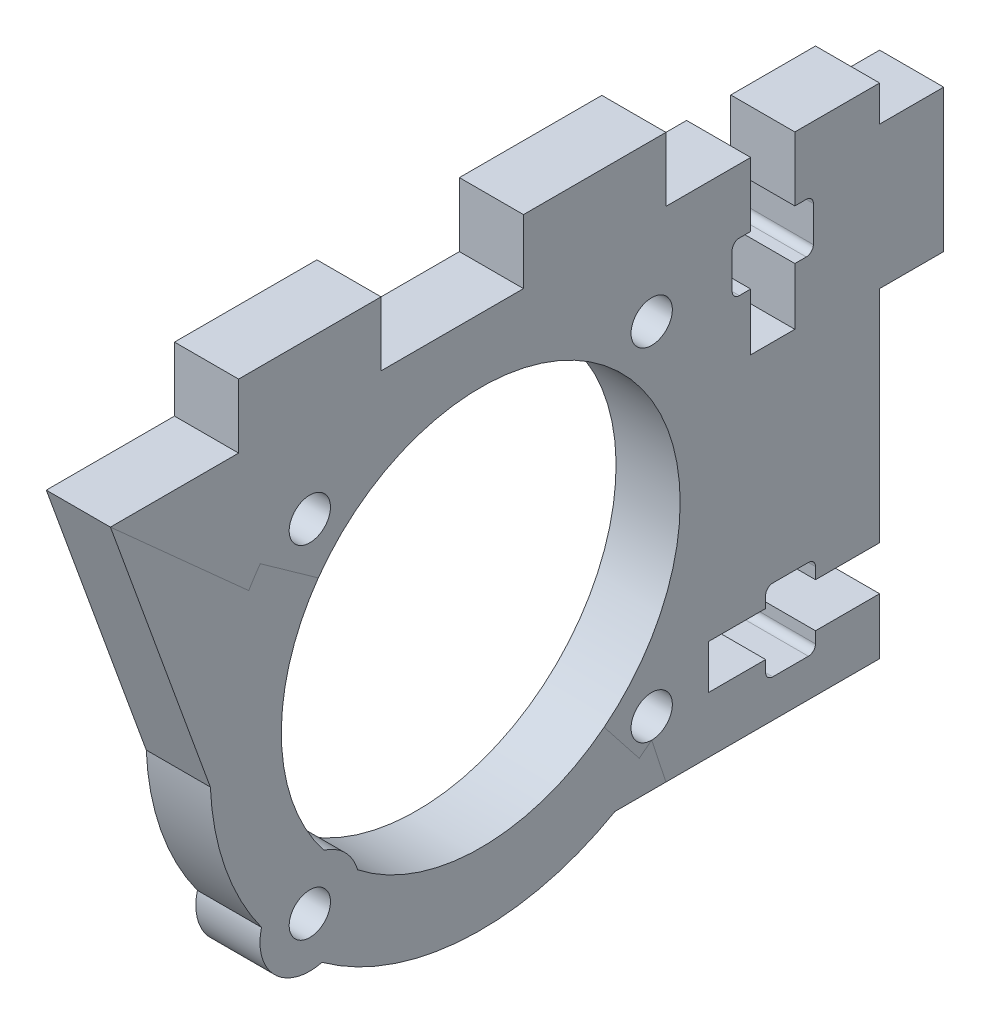
SolidWorks part; units mm, degrees
ref_plane "Front Plane" through (0, 0, 0) normal (0, 0, 1) x (1, 0, 0)
ref_plane "Top Plane" through (0, 0, 0) normal (0, 1, 0) x (1, 0, 0)
ref_plane "Right Plane" through (0, 0, 0) normal (1, 0, 0) x (0, 0, -1)
sketch "Sketch1" plane through (0, 0, 0) normal (1, 0, 0) x (0, 0, -1)
  line L0 (0, 0) -> (0, -35)
  line L1 (0, -35) -> (-54, 0)
  line L2 (-54, 0) -> (0, 0)
  dimension "D1" = 35
  dimension "D2" = 54
extrude "Boss-Extrude1" add sketch "Sketch1" along normal blind 4.5
sketch "Sketch2" plane through (4.5, 0, 0) normal (1, 0, 0) x (0, 0, -1)
  line L0 (0, -35) -> (0, 0) construction
  line L1 (-4.5, -2.5) -> (4.5, -2.5)
  line L2 (-4.5, -2.5) -> (-4.5, -12.5)
  line L3 (-4.5, -12.5) -> (4.5, -12.5)
  line L4 (4.5, -2.5) -> (4.5, -12.5)
  line L5 (-4.5, -2.5) -> (4.5, -12.5) construction
  line L6 (-4.5, -12.5) -> (4.5, -2.5) construction
  line L7 (0, 0) -> (-54, 0) construction
  point P0 (0, -7.5)
  dimension "D1" = 10
  dimension "D2" = 7.5
  dimension "D3" = 4.5
extrude "Boss-Extrude2" add sketch "Sketch2" against normal through all
sketch "Sketch3" plane through (4.5, 0, 0) normal (1, 0, 0) x (0, 0, -1)
  line L0 (0, -35) -> (-15, -35)
  line L1 (0, -25) -> (-54, 0)
  line L4 (0, -35) -> (0, -12.5) construction
  line L5 (0, -25) -> (0, -35)
  line L6 (-54, 0) -> (-15, -35)
  dimension "D1" = 15
  dimension "D2" = 10
extrude "Boss-Extrude3" add sketch "Sketch3" against normal through all
sketch "Sketch4" plane through (4.5, 0, 0) normal (1, 0, 0) x (0, 0, -1)
  line L0 (0, -29.5) -> (-12, -29.5) construction
  line L1 (0, -35) -> (0, -12.5) construction
  line L2 (0, -27.95) -> (-12, -27.95) construction
  line L3 (-12, -27.95) -> (-12, -31.05) construction
  line L4 (0, -31.05) -> (0, -27.95)
  line L5 (0, -27.95) -> (-4.5, -27.95)
  line L6 (-4.5, -27.95) -> (-4.5, -27.15)
  line L7 (-5, -26.65) -> (-7.5, -26.65)
  line L8 (-8, -27.15) -> (-8, -27.95)
  line L9 (-8, -27.95) -> (-12, -27.95)
  line L10 (-12, -27.95) -> (-12, -31.05)
  line L12 (0, -31.05) -> (-12, -31.05) construction
  line L13 (-8, -31.05) -> (-12, -31.05)
  line L14 (-8, -31.85) -> (-8, -31.05)
  line L15 (-5, -32.35) -> (-7.5, -32.35)
  line L16 (-4.5, -31.05) -> (-4.5, -31.85)
  line L17 (0, -31.05) -> (-4.5, -31.05)
  line L18 (4.5, -12.5) -> (4.5, -2.5) construction
  line L19 (0, -18.5) -> (-33.3857, -18.5) construction
  line L20 (-54, 0) -> (-15, -35) construction
  line L37 (0, -31.05) -> (-12, -31.05) construction
  arc A0 (-8, -31.85) -> (-7.5, -32.35) centre (-7.5, -31.85) ccw
  arc A1 (-5, -32.35) -> (-4.5, -31.85) centre (-5, -31.85) ccw
  arc A2 (-4.5, -27.15) -> (-5, -26.65) centre (-5, -27.15) ccw
  arc A3 (-7.5, -26.65) -> (-8, -27.15) centre (-7.5, -27.15) ccw
  point P10 (4.5, -7.5)
  point P20 (-8, -32.35)
  point P23 (-4.5, -32.35)
  point P26 (-4.5, -26.65)
  point P29 (-8, -26.65)
  dimension "D7" = 0.5
  dimension "D1" = 12
  dimension "D2" = 1.55
  dimension "D3" = 2.85
  dimension "D4" = 3.5
  dimension "D5" = 8
  dimension "D6" = 22
extrude "Cut-Extrude1" cut sketch "Sketch4" against normal through all
sketch "Sketch5" plane through (4.5, 0, 0) normal (1, 0, 0) x (0, 0, -1)
  line L0 (0, 0) -> (-54, 0) construction
  line L1 (-25, 4.5) -> (-15, 4.5)
  line L2 (-25, 4.5) -> (-25, 0)
  line L3 (0, 0) -> (-54, 0) construction
  line L4 (-15, 4.5) -> (-15, 0)
  line L5 (-25, 4.5) -> (-20, 0) construction
  line L6 (-20, 0) -> (-15, 4.5) construction
  line L7 (-30, 0) -> (-30, 4.5) construction
  line L8 (-40, 0) -> (-45, 4.5) construction
  line L9 (-35, 4.5) -> (-40, 0) construction
  line L10 (-45, 4.5) -> (-45, 0)
  line L12 (-35, 4.5) -> (-35, 0)
  line L13 (-35, 4.5) -> (-45, 4.5)
  line L14 (-20, 0) -> (-15, 4.5) construction
  line L15 (-15, 0) -> (-25, 0)
  line L16 (-35, 0) -> (-45, 0)
  point P0 (-20, 0)
  point P14 (-40, 0)
  dimension "D3" = 4.5
  dimension "D1" = 20
  dimension "D2" = 10
  dimension "D4" = 20
  dimension "D5" = 5
extrude "Boss-Extrude4" add sketch "Sketch5" against normal through all
sketch "Sketch8" [suppressed] plane through (4.5, 0, 0) normal (1, 0, 0) x (0, 0, -1)
  line L0 (-15, -30) -> (-27, -30) construction
  line L1 (-15, -35) -> (-27, -35)
  line L2 (-15, -25) -> (-27, -25)
  line L3 (-15, -35) -> (0, -35) construction
  line L4 (-15, -25) -> (-15, -35)
  arc A1 (-27, -25) -> (-27, -35) centre (-27, -30) ccw
  dimension "D5" = 5
  dimension "D1" = 0
  dimension "D2" = 12
  dimension "D3" = 0
  dimension "D4" = 10
extrude "Boss-Extrude5" [suppressed] add sketch "Sketch8" against normal up to surface (4.5 mm away) up to face at (0, -17.3125, 11.9375)
sketch "Sketch9" [suppressed] plane through (4.5, 0, 0) normal (1, 0, 0) x (0, 0, -1)
  line L0 (-27, -30) -> (-22, -30) construction
  line L1 (-27, -27) -> (-22, -27)
  line L2 (-27, -33) -> (-22, -33)
  arc A0 (-27, -27) -> (-27, -33) centre (-27, -30) ccw
  arc A1 (-22, -33) -> (-22, -27) centre (-22, -30) ccw
  point P3 (-24.5, -30)
  dimension "D1" = 3
  dimension "D2" = 5
extrude "Cut-Extrude3" [suppressed] cut sketch "Sketch9" against normal through all
sketch "Sketch10" plane through (0, 0, 0) normal (-1, 0, 0) x (0, 0, 1)
  line L0 (15, -35) -> (54, -12)
  line L1 (54, -12) -> (54, 0)
  line L3 (54, 0) -> (15, -35)
  dimension "D1" = 12
extrude "Boss-Extrude6" [suppressed] add sketch "Sketch10" against normal through all
sketch "Sketch6" plane through (4.5, 0, 0) normal (1, 0, 0) x (0, 0, -1)
  line L0 (-30, 0) -> (-30, -11) construction
  line L1 (-25, 0) -> (-35, 0) construction
  line L2 (-28.45, -11) -> (-31.55, -11) construction
  line L3 (-31.55, -11) -> (-31.55, 0) construction
  line L4 (-28.45, 0) -> (-31.55, 0)
  line L5 (-31.55, 0) -> (-31.55, -4.5)
  line L6 (-31.55, -4.5) -> (-32.35, -4.5)
  line L7 (-32.85, -5) -> (-32.85, -7.5)
  line L8 (-32.35, -8) -> (-31.55, -8)
  line L9 (-31.55, -8) -> (-31.55, -11)
  line L10 (-31.55, -11) -> (-28.45, -11)
  line L11 (-28.45, -11) -> (-28.45, 0) construction
  line L12 (-28.45, -8) -> (-28.45, -11)
  line L13 (-27.65, -8) -> (-28.45, -8)
  line L14 (-27.15, -5) -> (-27.15, -7.5)
  line L15 (-28.45, -4.5) -> (-27.65, -4.5)
  line L16 (-28.45, 0) -> (-28.45, -4.5)
  arc A0 (-32.85, -7.5) -> (-32.35, -8) centre (-32.35, -7.5) ccw
  arc A1 (-32.35, -4.5) -> (-32.85, -5) centre (-32.35, -5) ccw
  arc A2 (-27.65, -4.5) -> (-27.15, -5) centre (-27.65, -5) cw
  arc A3 (-27.15, -7.5) -> (-27.65, -8) centre (-27.65, -7.5) cw
  point P12 (-32.85, -8)
  point P15 (-32.85, -4.5)
  point P26 (-27.15, -4.5)
  point P27 (-27.15, -8)
  dimension "D2" = 1.55
  dimension "D4" = 3.5
  dimension "D6" = 0.5
  dimension "D1" = 11
  dimension "D3" = 8
  dimension "D5" = 2.85
extrude "Cut-Extrude2" [suppressed] cut sketch "Sketch6" against normal through all
sketch "Sketch11" plane through (0, 0, 0) normal (-1, 0, 0) x (0, 0, 1)
  line L0 (7.5, 0) -> (7.5, -12) construction
  line L1 (0, 0) -> (15, 0) construction
  line L2 (5.95, -12) -> (9.05, -12)
  line L3 (9.05, -12) -> (9.05, -8)
  line L4 (9.05, -8) -> (9.85, -8)
  line L5 (10.35, -7.5) -> (10.35, -5)
  line L6 (9.85, -4.5) -> (9.05, -4.5)
  line L7 (9.05, -4.5) -> (9.05, 0)
  line L8 (9.05, 0) -> (5.95, 0)
  line L9 (9.05, -8) -> (9.05, -4.5) construction
  line L10 (0, 0) -> (15, 0) construction
  line L11 (5.95, -8) -> (5.95, -4.5) construction
  line L12 (5.95, -4.5) -> (5.95, 0)
  line L13 (5.15, -4.5) -> (5.95, -4.5)
  line L14 (4.65, -7.5) -> (4.65, -5)
  line L15 (5.95, -8) -> (5.15, -8)
  line L16 (5.95, -12) -> (5.95, -8)
  arc A0 (10.35, -5) -> (9.85, -4.5) centre (9.85, -5) ccw
  arc A1 (5.15, -4.5) -> (4.65, -5) centre (5.15, -5) ccw
  arc A2 (9.85, -8) -> (10.35, -7.5) centre (9.85, -7.5) ccw
  arc A3 (4.65, -7.5) -> (5.15, -8) centre (5.15, -7.5) ccw
  point P11 (7.5, 0)
  point P22 (10.35, -4.5)
  point P25 (4.65, -4.5)
  point P28 (10.35, -8)
  point P31 (4.65, -8)
  dimension "D7" = 0.5
  dimension "D1" = 12
  dimension "D3" = 2.85
  dimension "D8" = 0.5
  dimension "D2" = 3.5
  dimension "D4" = 8
  dimension "D5" = 1.55
  dimension "D6" = 0
extrude "Cut-Extrude4" cut sketch "Sketch11" against normal through all
sketch "Sketch12" plane through (0, 0, 0) normal (-1, 0, 0) x (0, 0, 1)
  line L0 (28, -18.5) -> (16, -6.5) construction
  line L1 (28, -18.5) -> (28, -4.5) construction
  line L2 (28, -18.5) -> (40, -6.5) construction
  line L3 (28, -18.5) -> (14, -18.5) construction
  line L4 (28, -18.5) -> (16, -30.5) construction
  line L5 (28, -18.5) -> (16, -6.5) construction
  line L6 (0, -27.95) -> (0, -12.5) construction
  line L7 (25, 0) -> (35, 0) construction
  circle A0 centre (28, -18.5) radius 14
  circle A1 centre (16, -6.5) radius 1.45
  circle A2 centre (40, -6.5) radius 1.45
  circle A3 centre (16, -30.5) radius 1.45
  dimension "D1" = 28
  dimension "D2" = 2.9
  dimension "D3" = 12
  dimension "D4" = 45
  dimension "D5" = 28
  dimension "D6" = 18.5
extrude "FanCutout" cut sketch "Sketch12" against normal through all
sketch "Sketch13" plane through (0, 0, 0) normal (-1, 0, 0) x (0, 0, 1)
  line L0 (39.4071, -10.3834) -> (43.481, -7.4847)
  line L1 (19.3358, -29.4969) -> (16.2414, -33.4243)
  line L6 (28, -18.5) -> (54, 0) construction
  line L7 (28, -18.5) -> (15, -35) construction
  arc A0 (19.3358, -29.4969) -> (39.4071, -10.3834) centre (28, -18.5) ccw
  arc A1 (16.2414, -33.4243) -> (43.481, -7.4847) centre (28, -18.5) ccw
  arc A3 (40.4722, -12.1404) -> (20.333, -30.214) centre (28, -18.5) ccw construction
  dimension "D1" = 5
extrude "Boss-Extrude7" add sketch "Sketch13" against normal through all
sketch "Sketch14" plane through (0, 0, 0) normal (-1, 0, 0) x (0, 0, 1)
  line L0 (28, -4.5) -> (28, -32.5) construction
  line L1 (28, -18.5) -> (40, -30.5) construction
  circle A0 centre (28, -18.5) radius 14 construction
  circle A1 centre (40, -30.5) radius 3.5
  dimension "D2" = 7
  dimension "D1" = 45
  dimension "D3" = 12
extrude "Boss-Extrude8" add sketch "Sketch14" against normal through all
sketch "Sketch15" plane through (0, 0, 0) normal (-1, 0, 0) x (0, 0, 1)
  line L0 (42.4749, -32.9749) -> (28, -18.5) construction
  arc A0 (39.1388, -33.8924) -> (43.3924, -29.6388) centre (40, -30.5) ccw construction
  circle A1 centre (40, -30.5) radius 1.45
  dimension "D1" = 2.9
extrude "Cut-Extrude6" cut sketch "Sketch15" against normal through all
sketch "Sketch16" [suppressed] plane through (4.5, 0, 0) normal (1, 0, 0) x (0, 0, -1)
  line L0 (0, -34.5) -> (-39, -34.5) construction
  line L1 (0, -27.95) -> (0, -12.5) construction
  line L2 (-15, -34.5) -> (-39, -34.5) construction
  line L3 (-15, -38.5) -> (-39, -38.5)
  line L4 (-15, -30.5) -> (-39, -30.5)
  arc A0 (-15, -38.5) -> (-15, -30.5) centre (-15, -34.5) ccw
  arc A1 (-39, -30.5) -> (-39, -38.5) centre (-39, -34.5) ccw
  point P5 (-27, -34.5)
  point P12 (0, -20.225)
  dimension "D1" = 4
  dimension "D2" = 34.5
  dimension "D3" = 39
  dimension "D4" = 15
extrude "Boss-Extrude9" [suppressed] add sketch "Sketch16" against normal through all
sketch "Sketch17" [suppressed] plane through (4.5, 0, 0) normal (1, 0, 0) x (0, 0, -1)
  line L0 (-43, -34.5) -> (0, -34.5) construction
  line L1 (0, -27.75) -> (0, -12.5) construction
  line L2 (-26.5, -34.5) -> (-26.5, -20.0064) construction
  arc A0 (-42.1823, -32.0766) -> (-39, -38.5) centre (-39, -34.5) ccw construction
  circle A1 centre (-39, -34.5) radius 1.55
  circle A2 centre (-14, -34.5) radius 1.55
  dimension "D1" = 2.9
  dimension "D2" = 12.5
extrude "Cut-Extrude7" [suppressed] cut sketch "Sketch17" against normal through all
sketch "Sketch18" [suppressed] plane through (4.5, 0, 0) normal (1, 0, 0) x (0, 0, -1)
  line L0 (-15, -38.5) -> (0, -35)
  line L1 (0, -35) -> (-11.0314, -35)
  line L2 (-11.0314, -35) -> (-15, -38.5)
extrude "Boss-Extrude10" [suppressed] add sketch "Sketch18" against normal through all
sketch "Sketch20" [suppressed] plane through (4.5, 0, 0) normal (1, 0, 0) x (0, 0, -1)
  line L0 (0, -35) -> (0, -31.05) construction
  line L1 (-9, -38) -> (-37.9081, -38)
  line L2 (-40.7232, -36.0371) -> (-54, 0)
  line L3 (-54, 0) -> (-15, -35)
  line L4 (-15, -35) -> (-6, -35)
  line L5 (-9, -38) -> (-6, -35)
  line L6 (-40.7232, -36.0371) -> (-40, -38) construction
  line L7 (-40, -38) -> (-37.9081, -38) construction
  arc A1 (-37.9081, -38) -> (-40.7232, -36.0371) centre (-37.9081, -35) cw
  point P0 (0, -33.025)
  point P14 (-40, -38)
  dimension "D3" = 6
  dimension "D4" = 3
  dimension "D1" = 40
  dimension "D2" = 3
  dimension "D5" = 135
extrude "Boss-Extrude11" [suppressed] add sketch "Sketch20" against normal through all
sketch "Sketch21" [suppressed] plane through (4.5, 0, 0) normal (1, 0, 0) x (0, 0, -1)
  line L0 (0, -34.5) -> (-41.2895, -34.5) construction
  line L1 (0, -35) -> (0, -31.05) construction
  line L2 (-54, 0) -> (-40.7232, -36.0371) construction
  line L3 (0, -27.95) -> (0, -12.5) construction
  circle A0 centre (-36, -34.5) radius 1.45
  circle A1 centre (-11, -34.5) radius 1.45
  dimension "D2" = 2.9
  dimension "D3" = 2.9
  dimension "D1" = 25
  dimension "D4" = 34.5
  dimension "D5" = 11
extrude "Cut-Extrude8" [suppressed] cut sketch "Sketch21" against normal through all
sketch "Sketch22" [suppressed] plane through (4.5, 0, 0) normal (1, 0, 0) x (0, 0, -1)
  line L0 (0, -27.95) -> (0, -12.5) construction
  line L1 (-25, 0) -> (-35, 0) construction
  circle A0 centre (-28, -18) radius 13.25
  dimension "D2" = 18
  dimension "D3" = 26.5
  dimension "D1" = 28
extrude "Cut-Extrude9" [suppressed] cut sketch "Sketch22" against normal through all
sketch "Sketch24" plane through (0, 0, 0) normal (-1, 0, 0) x (0, 0, 1)
  line L0 (15, -35) -> (20, -35)
  line L1 (20, -35) -> (16, -31.95)
  line L2 (16, -31.95) -> (15, -35)
  circle A0 centre (16, -30.5) radius 1.45 construction
  dimension "D1" = 5
extrude "Boss-Extrude13" add sketch "Sketch24" against normal through all
sketch "Sketch25" plane through (0, 0, 0) normal (-1, 0, 0) x (0, 0, 1)
  line L0 (54, 0) -> (46.9826, -19.3121)
  line L1 (46.9826, -19.3121) -> (44.2874, -8.7164)
  line L2 (44.2874, -8.7164) -> (54, 0)
  arc A0 (43.3924, -29.6388) -> (44.2874, -8.7164) centre (28, -18.5) ccw construction
extrude "Boss-Extrude15" add sketch "Sketch25" against normal through all
equation "\"X-ROD-SPACING\"=45"
equation "\"Y-ROD-SPACING\"=75"
equation "\"Z-ROD-SPACING\"=17.5"
equation "\"Y-BED-OFFSET\"=2"
equation "\"Y-BED-ROD-INSET\"=3.5"
equation "\"Y-BED-SCREW-SPACING\"=209"
equation "\"Y-BED-SCREW-CUTOUT-SLOT-HEIGHT\"=2"
equation "\"T-SLOT-NUT-FILLET-RADIUS\"=0.5"
equation "\"T-SLOT-SCREW-SHAFT-RADIUS\"=1.55"
equation "\"T-SLOT-SCREW-SHAFT-CUTOUT-LENGTH\"=11.0"
equation "\"T-SLOT-NUT-DEPTH\"=3.5"
equation "\"T-SLOT-NUT-WIDTH\"=2.85"
equation "\"T-SLOT-NUT-END-DISTANCE\"=8"
equation "\"ACRYLIC-THICKNESS\"=10"
equation "\"ACRYLIC-THICKNESS2\"=4.5"
equation "\"ACRYLIC-TAB-CUTOUT-SIZE\"=\"ACRYLIC-THICKNESS\"+\"ACRYLIC-TAB-TOLERANCE\"*2"
equation "\"ACRYLIC-TAB-WIDTH\"=\"ACRYLIC-THICKNESS\""
equation "\"ACRYLIC-M3-HOLE\"=2.9"
equation "\"SMOOTHROD-CAP-SCREW-DISTANCE\"=20"
equation "\"FRAME-WIDTH-INNER\"=370"
equation "\"NEMA17-HOLE-SPACING\"=31"
equation "\"NEMA17-CENTRAL-CUTOUT\"=22.5"
equation "\"Z-BRACKET-REACH\"=55"
equation "\"Z-ROD-INSET\"=16"
equation "\"TOP-BRACKET-SPACING\"=40"
equation "\"SMOOTHROD-X-LENGTH\"=350"
equation "\"SMOOTHROD-Y-LENGTH\"=350"
equation "\"SMOOTHROD-Z-LENGTH\"=350"
equation "\"SMOOTHROD-TIGHTENING-HEADROOM\"=.25"
equation "\"LEADSCREW-Z-LENGTH\"=300"
equation "\"SCREW-LENGTH-FRAME\"=\"ACRYLIC-THICKNESS\" + 10"
equation "\"SCREW-LENGTH-MOTOR\"=\"ACRYLIC-THICKNESS\" + 5"
equation "\"SCREW-LENGTH-EXTRUDER\"=28"
equation "\"SCREW-HEAD-RADIUS\"=6"
equation "\"PRINTED-X-SMOOTHROD-DIAMETER\"=9.0"
equation "\"PRINTED-X-SMOOTHROD-CUTOUT\"=10"
equation "\"PRINTED-X-BASE-HEIGHT\"=10"
equation "\"PRINTED-LM8UU-CUTOUT-SIZE\"=15.5"
equation "\"PRINTED-LM8UU-CUTOUT-LENGTH\"=24.5"
equation "\"PRINTED-X-IDLER-HEIGHT\"=16"
equation "\"PSU-MOUNTING-WIDTH\"=95"
equation "\"PSU-MOUNTING-HEIGHT\"=177"
equation "\"Y-BELT-TO-ROD-DISTANCE\"=20"
equation "\"SPOOL-HOLDER-ROD-SPACING\"=150"
equation "\"ACRYLIC-X-CARRIAGE-WIDTH\"=55"
equation "\"ACRYLIC-X-CARRIAGE-HEIGHT\"=75"
equation "\"ACRYLIC-X-CARRIAGE-SCREW-SPACING-X\"=15"
equation "\"ACRYLIC-X-CARRIAGE-SCREW-SPACING-Y\"=33"
equation "\"ACRYLIC-X-CARRIAGE-CENTER-TAB-SPACING\"=14"
equation "\"ACRYLIC-X-CARRIAGE-EXTRUDER-SHELF-DEPTH\"=\"ACRYLIC-X-CARRIAGE-EXTRUDER-OFFSET\" + 28"
equation "\"D2@Sketch1\"=\"ACRYLIC-X-CARRIAGE-EXTRUDER-SHELF-DEPTH\""
equation "\"D1@Boss-Extrude1\"=\"ACRYLIC-THICKNESS2\""
equation "\"D1@Sketch2\"=\"ACRYLIC-TAB-WIDTH\""
equation "\"D3@Sketch2\"=\"ACRYLIC-THICKNESS2\""
equation "\"ACRYLIC-X-CARRIAGE-LM8UU-CUTOUT-WIDTH\"=24.25"
equation "\"ACRYLIC-X-CARRIAGE-EXTRUDER-BRACE-SPACING\"=23"
equation "\"ACRYLIC-X-CARRIAGE-EXTRUDER-BRACE-HEIGHT\"=35"
equation "\"D1@Sketch1\"=\"ACRYLIC-X-CARRIAGE-EXTRUDER-BRACE-HEIGHT\""
equation "\"D1@Sketch4\"=\"T-SLOT-SCREW-SHAFT-CUTOUT-LENGTH\"+1"
equation "\"D2@Sketch4\"=\"T-SLOT-SCREW-SHAFT-RADIUS\""
equation "\"D3@Sketch4\"=\"T-SLOT-NUT-WIDTH\""
equation "\"D4@Sketch4\"=\"T-SLOT-NUT-DEPTH\""
equation "\"D5@Sketch4\"=\"T-SLOT-NUT-END-DISTANCE\""
equation "\"D7@Sketch4\"=\"T-SLOT-NUT-FILLET-RADIUS\""
equation "\"ACRYLIC-X-CARRIAGE-EXTRUDER-BRACE-SCREW-SPACING\"=22"
equation "\"D6@Sketch4\"=\"ACRYLIC-X-CARRIAGE-EXTRUDER-BRACE-SCREW-SPACING\""
equation "\"ACRYLIC-X-CARRIAGE-EXTRUDER-BRACE-TAB-OFFSET\"=20"
equation "\"D1@Sketch5\"=\"ACRYLIC-X-CARRIAGE-EXTRUDER-BRACE-TAB-OFFSET\""
equation "\"D2@Sketch5\"=\"ACRYLIC-TAB-WIDTH\""
equation "\"D3@Sketch5\"=\"ACRYLIC-THICKNESS2\""
equation "\"ACRYLIC-X-CARRIAGE-EXTRUDER-OFFSET\"=26"
equation "\"ACRYLIC-X-CARRIAGE-EXTRUDER-ANGLE\"=90"
equation "\"D1@Sketch6\"=\"T-SLOT-SCREW-SHAFT-CUTOUT-LENGTH\""
equation "\"D2@Sketch6\"=\"T-SLOT-SCREW-SHAFT-RADIUS\""
equation "\"D3@Sketch6\"=\"T-SLOT-NUT-END-DISTANCE\""
equation "\"D4@Sketch6\"=\"T-SLOT-NUT-DEPTH\""
equation "\"D5@Sketch6\"=\"T-SLOT-NUT-WIDTH\""
equation "\"D6@Sketch6\"=\"T-SLOT-NUT-FILLET-RADIUS\""
equation "\"D1@Sketch11\"=\"T-SLOT-SCREW-SHAFT-CUTOUT-LENGTH\"+1"
equation "\"D2@Sketch11\"=\"T-SLOT-NUT-DEPTH\""
equation "\"D3@Sketch11\"=\"T-SLOT-NUT-WIDTH\""
equation "\"D4@Sketch11\"=\"T-SLOT-NUT-END-DISTANCE\""
equation "\"D5@Sketch11\"=\"T-SLOT-SCREW-SHAFT-RADIUS\""
equation "\"D7@Sketch11\"=\"T-SLOT-NUT-FILLET-RADIUS\""
equation "\"D8@Sketch11\"=\"T-SLOT-NUT-FILLET-RADIUS\""
equation "\"D2@Sketch12\"=\"ACRYLIC-M3-HOLE\""
equation "\"D1@Sketch15\"=\"ACRYLIC-M3-HOLE\""
equation "\"D1@Sketch17\"=\"ACRYLIC-M3-HOLE\""
equation "\"D2@Sketch21\"=\"ACRYLIC-M3-HOLE\""
equation "\"D3@Sketch21\"=\"ACRYLIC-M3-HOLE\""
